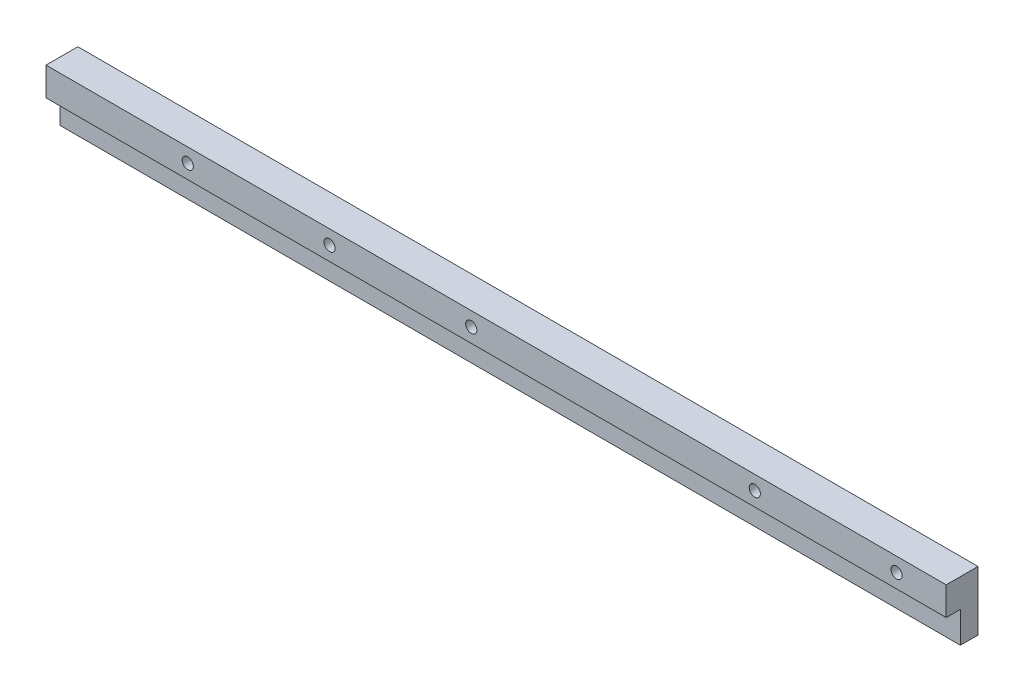
SolidWorks part; units mm, degrees
note: The reader was unsure of these and kept them because the rebuilt part matched: shared geometry of "Sketch2<3>".
ref_plane "Front Plane" through (0, 0, 0) normal (0, 0, 1) x (1, 0, 0)
ref_plane "Top Plane" through (0, 0, 0) normal (0, 1, 0) x (1, 0, 0)
ref_plane "Right Plane" through (0, 0, 0) normal (1, 0, 0) x (0, 0, -1)
sketch "Sketch1" plane through (0, 0, 0) normal (0, 0, 1) x (1, 0, 0)
  line L0 (6.5929, 7.3704) -> (176.701, 203.0574)
  line L1 (6.5929, 7.3704) -> (176.701, 7.3704)
  line L2 (176.701, 203.0574) -> (292.6093, 77.8877)
  line L3 (176.701, 203.0574) -> (176.701, 7.3704)
  line L4 (6.5929, 7.3704) -> (4.0986, 9.5386)
  line L6 (4.0986, 9.5386) -> (174.2067, 205.2256)
  line L10 (174.2067, 205.2256) -> (176.701, 203.0574)
  line L11 (292.6093, 77.8877) -> (294.8662, 79.9776)
  line L12 (294.8662, 79.9776) -> (176.701, 207.5845)
  line L13 (176.701, 203.0574) -> (176.701, 207.5845)
  line L14 (176.701, 207.5845) -> (174.2067, 205.2256)
  line L15 (4.0986, 9.5386) -> (6.5929, 7.3704)
  line L16 (6.5929, 7.3704) -> (9.3301, 4.6332)
  line L17 (9.3301, 4.6332) -> (179.222, 200.3349)
  line L18 (292.6093, 77.8877) -> (289.803, 75.306)
  line L19 (289.803, 75.306) -> (176.701, 197.4308)
  dimension "D1" = 42.8
  dimension "D3" = 90
  dimension "D4" = 90
  dimension "D5" = 41
extrude "Boss-Extrude1" add sketch "Sketch1" along normal blind 177.8 contours L10 L6 L4 L0 | L13 L14 L10 | L13 L2 L11 L12 | L1 L17 L3 L0 | L19 L18 L2 L17 | L3 L17 L2
ref_plane "Plane1" through (0, 0, 0) normal (0, 0, -1) x (-1, 0, 0)
sketch "Sketch2" plane through (0, 0, 0) normal (0, 0, -1) x (-1, 0, 0)
  line L4 (-294.8662, 79.9776) -> (-176.701, 207.5845) construction
  line L5 (-176.701, 207.5845) -> (-294.8662, 79.9776)
  line L6 (-176.701, 207.5845) -> (-4.0362, 9.4669)
  line L11 (-294.8662, 308.5776) -> (-4.0362, 308.5776)
  line L12 (-4.0362, 308.5776) -> (-4.0362, 9.4669)
  line L14 (-294.8662, 308.5776) -> (-294.8662, 79.9776)
  line L15 (-4.0986, 9.5386) -> (-174.2067, 205.2256) construction
  circle A6 centre (-109.5518, 215.6074) radius 6.35
  circle A7 centre (-50.0992, 143.6384) radius 6.35
  circle A8 centre (0, 64.0701) radius 6.35
  dimension "D4" = 94.0268
  dimension "D1" = 228.6
  dimension "D2" = 93.3497
  dimension "D3" = 290.83
extrude "Boss-Extrude2" add sketch "Sketch2" against normal blind 3.175
ref_plane "Plane2" through (0, 0, 177.8) normal (0, 0, 1) x (1, 0, 0)
ref_plane "Plane3" through (0, 0, 88.9) normal (0, 0, 1) x (1, 0, 0)
mirror "Mirror1" about plane through (0, 0, 88.9) normal (0, 0, 1) of "Boss-Extrude2"
sketch "Sketch3" plane through (-2.3884, 2.0762, 0) normal (-0.7547, 0.6561, 0) x (0.6561, 0.7547, 0)
  line L0 (0, -88.9) -> (269.1756, -88.9) construction
  line L1 (-55, -88.9) -> (55, -88.9) construction
  line L2 (269.1756, -174.625) -> (269.1756, -3.175) construction
  line L3 (9.8879, -115.3039) -> (147.0479, -115.3039)
  line L4 (147.0479, -115.3039) -> (146.9349, 0)
  line L5 (235.5345, 0) -> (9.7927, 0) construction
  line L6 (146.9349, 0) -> (210.4349, 0)
  line L7 (272.5923, 0) -> (9.7927, 0) construction
  line L8 (210.4349, 0) -> (210.4349, -115.3039)
  line L9 (210.4349, -115.3039) -> (147.0479, -115.3039)
  line L10 (147.0479, -115.3039) -> (210.4349, -115.3039)
  line L11 (9.8879, -174.625) -> (9.8879, -3.175) construction
  dimension "D1" = 63.5
  dimension "D3" = 137.16
extrude "Cut-Extrude1" cut sketch "Sketch3" against normal blind 7.62
sketch "Sketch4" plane through (0, 0, 3.175) normal (0, 0, 1) x (1, 0, 0)
  line L0 (176.701, 207.5845) -> (4.0362, 9.4669) construction
  circle A0 centre (115.1385, 136.947) radius 35.56
extrude "Cut-Extrude2" cut sketch "Sketch4" against normal blind 5.08
sketch "Sketch5" plane through (0, 0, 0) normal (0, 0, -1) x (-1, 0, 0)
  line L0 (-4.0362, 308.5776) -> (-4.0362, 9.4669) construction
  line L1 (-4.0362, 87.8093) -> (23.7187, 87.8093)
  line L2 (-4.0362, 87.8093) -> (-4.0362, 41.2582)
  line L3 (-4.0362, 41.2582) -> (23.7187, 41.2582)
  line L4 (23.7187, 87.8093) -> (23.7187, 41.2582)
  line L5 (-294.8662, 308.5776) -> (-4.0362, 308.5776) construction
  circle A0 centre (0, 64.0701) radius 6.35
  line M4 (-4.0362, 9.4669) -> (-4.0362, 308.5776)
extrude "Boss-Extrude3" add sketch "Sketch5" against normal blind 3.175 contours L4 L1 L3 A0 M4
sketch "Sketch6" plane through (0, 0, 177.8) normal (0, 0, 1) x (1, 0, 0)
  line L1 (4.0362, 87.8093) -> (-23.7187, 87.8093)
  line L2 (4.0362, 87.8093) -> (4.0362, 41.2582)
  line L3 (4.0362, 41.2582) -> (-23.7187, 41.2582)
  line L4 (-23.7187, 87.8093) -> (-23.7187, 41.2582)
  circle A0 centre (0, 64.0701) radius 6.35
  line M6 (4.0362, 308.5776) -> (4.0362, 9.4669)
extrude "Boss-Extrude4" add sketch "Sketch6" against normal blind 3.175 contours L1 L4 L3 A0 M6
extrude "Cut-Extrude3" cut sketch "Sketch2<3>" against normal blind 203.2 contours A8
sketch "Sketch2<3>" plane through (0, 0, 0) normal (0, 0, -1) x (-1, 0, 0) same geometry as "Sketch2"
sketch "Sketch7" plane through (198.615, 183.9195, 0) normal (0.7337, 0.6794, 0) x (0, 0, -1)
  line L0 (-174.625, -141.6623) -> (-3.175, -141.6623) construction
  line L1 (-3.175, -141.6623) -> (-88.9, -141.6623) construction
  line L2 (-88.9, -141.6623) -> (-88.9, -123.8823) construction
  line L3 (-88.9, 55) -> (-88.9, -55) construction
  line L4 (-88.9, -123.8823) -> (-36.6474, -123.8823) construction
  line L5 (-36.6474, -123.8823) -> (-36.6474, -141.6623) construction
  line L6 (-36.6474, -141.6623) -> (-140.9512, -141.6623) construction
  line L7 (-140.9512, -141.6623) -> (-140.9512, -123.8823) construction
  line L8 (-140.9512, -123.8823) -> (-88.9, -123.8823) construction
  line L10 (-140.9512, -123.8823) -> (-36.6474, -123.8823)
  line L11 (-140.9512, -123.8823) -> (-140.9512, -141.6623)
  line L12 (-140.9512, -141.6623) -> (-36.6474, -141.6623)
  line L13 (-36.6474, -123.8823) -> (-36.6474, -141.6623)
  dimension "D1" = 17.78
extrude "Cut-Extrude4" cut sketch "Sketch7" against normal blind 7.62
sketch "Sketch8" plane through (0, 0, 0) normal (0, 0, -1) x (-1, 0, 0)
  line L0 (-294.8662, 79.9776) -> (-294.8662, 191.7376) construction
  line L1 (-294.8662, 308.5776) -> (-294.8662, 79.9776) construction
sketch "Sketch9" plane through (294.8662, 0, 0) normal (1, 0, 0) x (0, 0, -1)
  line L1 (0, 186.7117) -> (5.0949, 186.7117)
  line L2 (0, 186.7117) -> (0, 196.8717)
  line L3 (0, 196.8717) -> (5.0949, 196.8717)
  line L4 (5.0949, 186.7117) -> (5.0949, 196.8717)
  line L5 (0, 308.5776) -> (0, 79.9776) construction
  line L6 (5.0949, 196.8717) -> (11.4058, 196.8717)
  line L7 (5.0949, 196.8717) -> (5.0949, 175.5607)
  line L8 (5.0949, 175.5607) -> (11.4058, 175.5607)
  line L9 (11.4058, 196.8717) -> (11.4058, 175.5607)
  line M1 (0, 79.9776) -> (0, 308.5776)
  dimension "D1" = 10.16
extrude "Boss-Extrude5" add sketch "Sketch9" against normal blind 373.38 contours L1 L4 L3 M1 | L9 L6 L4 L7 L8
ref_plane "Plane4" through (0, 0, 88.9) normal (0, 0, 1) x (1, 0, 0)
mirror "Mirror2" about plane through (0, 0, 88.9) normal (0, 0, 1) of "Boss-Extrude5"
sketch "Sketch10" plane through (294.8662, 0, 0) normal (1, 0, 0) x (0, 0, -1)
  line L0 (0, 308.5776) -> (0, 79.9776) construction
  line L1 (0, 205.7357) -> (16.3899, 205.7357)
  line L2 (0, 205.7357) -> (0, 149.8827)
  line L3 (0, 149.8827) -> (16.3899, 149.8827)
  line L4 (16.3899, 205.7357) -> (16.3899, 149.8827)
extrude "Cut-Extrude5" cut sketch "Sketch10" against normal blind 50.8
sketch "Sketch11" plane through (0, 0, 0) normal (0, 0, -1) x (-1, 0, 0)
  line L0 (-294.8662, 308.5776) -> (-294.8662, 79.9776) construction
  line L1 (-294.8662, 209.1619) -> (-257.555, 209.1619)
  line L2 (-294.8662, 209.1619) -> (-294.8662, 139.1254)
  line L3 (-294.8662, 139.1254) -> (-257.555, 139.1254)
  line L4 (-257.555, 209.1619) -> (-257.555, 139.1254)
extrude "Cut-Extrude6" cut sketch "Sketch11" against normal blind 63.5
sketch "Sketch12" plane through (198.615, 183.9195, 0) normal (0.7337, 0.6794, 0) x (0, 0, -1)
  line L0 (-171.533, 28.0226) -> (-143.202, -115.1621)
  line L1 (-33.4545, -115.1621) -> (-6.2281, 28.0226)
extrude "Cut-Extrude-Thin3" cut sketch "Sketch12" against normal blind 1.27 thin thin type one direction reverse wall 3.302
sketch "Sketch13" plane through (198.615, 183.9195, 0) normal (0.7337, 0.6794, 0) x (0, 0, -1)
  line L0 (-171.533, 28.0226) -> (-171.3752, 27.2252)
  line L1 (-171.3752, 27.2252) -> (-168.2938, 28.6635)
  line L2 (-168.2938, 28.6635) -> (-171.533, 28.0226)
  line L3 (-168.2938, 28.6635) -> (-139.9628, -114.5212) construction
  line L4 (-143.202, -115.1621) -> (-140.1206, -113.7238)
  line L5 (-140.1206, -113.7238) -> (-139.9628, -114.5212)
  line L6 (-143.202, -115.1621) -> (-139.9628, -114.5212)
  line L7 (-171.533, 28.0226) -> (-143.202, -115.1621) construction
  line L8 (-171.533, 28.0226) -> (-143.202, -115.1621) construction
  line L9 (-9.4719, 28.6394) -> (-6.3826, 27.2098)
  line L10 (-33.4545, -115.1621) -> (-6.2281, 28.0226) construction
  line L11 (-6.3826, 27.2098) -> (-6.2281, 28.0226)
  line L12 (-6.2281, 28.0226) -> (-9.4719, 28.6394)
  line L13 (-36.6984, -114.5453) -> (-33.3027, -114.3636)
  line L14 (-33.4545, -115.1621) -> (-6.2281, 28.0226) construction
  line L15 (-33.3027, -114.3636) -> (-33.4545, -115.1621)
  line L16 (-33.4545, -115.1621) -> (-36.6984, -114.5453)
  dimension "D1" = 0.8128
  dimension "D2" = 0.8128
  dimension "D3" = 0.8128
  dimension "D4" = 0.8128
extrude "Boss-Extrude6" add sketch "Sketch13" against normal blind 1.27 separate body
sketch "Sketch14" plane through (0, 0, 3.175) normal (0, 0, 1) x (1, 0, 0)
  line L0 (4.0362, 308.5776) -> (4.0362, 9.4669) construction
  circle A0 centre (25.6262, 167.7264) radius 6.35
  dimension "D1" = 21.59
extrude "Cut-Extrude7" cut sketch "Sketch14" against normal blind 6.35
sketch "Sketch15" plane through (0, 0, 177.8) normal (0, 0, 1) x (1, 0, 0)
  circle A0 centre (25.6262, 167.7264) radius 6.35
extrude "Cut-Extrude8" cut sketch "Sketch15" against normal blind 6.35
sketch "Sketch16" plane through (0, 0, -11.4058) normal (0, 0, -1) x (-1, 0, 0)
  line L0 (-244.0662, 191.7917) -> (-4.0362, 191.7917) construction
  line L1 (-244.0662, 196.8717) -> (-244.0662, 186.7117) construction
  line L2 (-4.0362, 308.5776) -> (-4.0362, 9.4669) construction
  line L3 (-4.0362, 191.7917) -> (78.5138, 191.7917) construction
  line L4 (78.5138, 196.8717) -> (78.5138, 175.5607) construction
  circle A0 centre (-226.2862, 191.7917) radius 2
  circle A1 centre (-175.4862, 191.7917) radius 2
  circle A2 centre (-73.8862, 191.7917) radius 2
  circle A3 centre (-23.0862, 191.7917) radius 2
  circle A4 centre (27.7138, 191.7917) radius 2
  dimension "D1" = 50.8
  dimension "D5" = 50.8
  dimension "D2" = 50.8
  dimension "D3" = 101.6
  dimension "D4" = 50.8
extrude "Cut-Extrude9" cut sketch "Sketch16" against normal blind 203.2
sketch "Sketch17" plane through (0, 0, 189.2058) normal (0, 0, 1) x (1, 0, 0)
  line L0 (226.2862, 191.7917) -> (294.8662, 191.7376) construction
  circle A0 centre (272.0062, 191.7376) radius 2
  dimension "D1" = 45.72
extrude "Cut-Extrude10" cut sketch "Sketch17" against normal blind 50.8
sketch "Sketch18" plane through (198.615, 183.9195, 0) normal (0.7337, 0.6794, 0) x (0, 0, -1)
  line L0 (-170.825, -33.5095) -> (-170.825, -115.9129)
  line L1 (-170.825, -115.9129) -> (-148.0215, -115.9129)
  line L2 (-148.0215, -115.9129) -> (-165.1241, -33.5095)
  line L3 (-165.1241, -33.5095) -> (-170.825, -33.5095)
extrude "Cut-Extrude11" cut sketch "Sketch18" against normal blind 50.8
sketch "Sketch19" plane through (198.615, 183.9195, 0) normal (0.7337, 0.6794, 0) x (0, 0, -1)
  line L0 (-27.791, -115.9129) -> (-12.8356, -35.3555)
  line L1 (-12.8356, -35.3555) -> (-7.2062, -35.3555)
  line L2 (-7.2062, -35.3555) -> (-7.2062, -115.9129)
  line L3 (-7.2062, -115.9129) -> (-27.791, -115.9129)
extrude "Cut-Extrude12" cut sketch "Sketch19" against normal blind 135.636
sketch "Sketch20" plane through (0, 0, 177.8) normal (0, 0, 1) x (1, 0, 0)
  line L0 (294.8662, 308.5776) -> (4.0362, 308.5776) construction
  line L1 (162.8579, 292.5756) -> (264.4579, 292.5756)
  line L2 (162.8579, 292.5756) -> (162.8579, 241.7756)
  line L3 (162.8579, 241.7756) -> (264.4579, 241.7756)
  line L4 (264.4579, 292.5756) -> (264.4579, 241.7756)
  line L5 (169.2079, 292.4947) -> (258.1079, 292.4947)
  line L6 (169.2079, 292.4947) -> (169.2079, 273.4447)
  line L7 (169.2079, 273.4447) -> (258.1079, 273.4447)
  line L8 (258.1079, 292.4947) -> (258.1079, 273.4447)
  circle A0 centre (162.8579, 241.7756) radius 1.55
  circle A1 centre (162.8579, 292.5756) radius 1.55
  circle A2 centre (264.4579, 292.5756) radius 1.55
  circle A3 centre (264.4579, 241.7756) radius 1.55
  dimension "D3" = 16.002
  dimension "D1" = 101.6
  dimension "D2" = 50.8
  dimension "D4" = 6.35
  dimension "D5" = 88.9
  dimension "D6" = 19.05
extrude "Cut-Extrude13" cut sketch "Sketch20" against normal blind 25.4 contours L2 A1 L1 | L1 A1 L2 | L4 A2 L1 | L1 A2 L4 | L2 A0 L3 | L3 A0 L2 | L4 A3 L3 | L3 A3 L4 | L8 L5 L6 L7
sketch "Sketch22" plane through (0, 0, 0) normal (0, 0, -1) x (-1, 0, 0)
  line L0 (-294.8662, 308.5776) -> (-4.0362, 308.5776) construction
  line L1 (-264.5816, 292.5756) -> (-162.9816, 292.5756)
  line L2 (-264.5816, 292.5756) -> (-264.5816, 241.7756)
  line L3 (-264.5816, 241.7756) -> (-162.9816, 241.7756)
  line L4 (-162.9816, 292.5756) -> (-162.9816, 241.7756)
  line L5 (-258.2316, 292.5534) -> (-169.3316, 292.5534)
  line L6 (-258.2316, 292.5534) -> (-258.2316, 273.5034)
  line L7 (-258.2316, 273.5034) -> (-169.3316, 273.5034)
  line L8 (-169.3316, 292.5534) -> (-169.3316, 273.5034)
  circle A0 centre (-264.5816, 292.5756) radius 1.55
  circle A1 centre (-264.5816, 241.7756) radius 1.55
  circle A2 centre (-162.9816, 292.5756) radius 1.55
  circle A3 centre (-162.9816, 241.7756) radius 1.55
  dimension "D3" = 16.002
  dimension "D1" = 101.6
  dimension "D2" = 50.8
  dimension "D4" = 6.35
  dimension "D5" = 88.9
  dimension "D6" = 19.05
extrude "Cut-Extrude14" cut sketch "Sketch22" against normal blind 25.4 contours L1 A0 L2 | L2 A0 L1 | L2 A1 L3 | L3 A1 L2 | L4 A2 L1 | L1 A2 L4 | L4 A3 L3 | L3 A3 L4 | L8 L5 L6 L7
sketch "Sketch23" plane through (0, 0, 0) normal (0, 0, -1) x (-1, 0, 0)
  line L0 (-292.2866, 77.5908) -> (-174.4076, 204.953) construction
  line L1 (-292.6093, 77.8877) -> (-289.803, 75.306) construction
  line L2 (-176.701, 207.5845) -> (-4.0362, 9.4669) construction
  line L3 (-7.2586, 7.3704) -> (-177.0204, 202.13)
  line L4 (-6.5929, 7.3704) -> (-11.7063, 7.3704) construction
  circle A0 centre (-282.4885, 88.1771) radius 1.5
  circle A1 centre (-262.696, 109.5619) radius 1.5
  circle A2 centre (-243.4899, 130.3131) radius 1.5
  circle A3 centre (-222.238, 153.2747) radius 1.5
  circle A4 centre (-17.5669, 19.1965) radius 1.5
  circle A5 centre (-33.1684, 37.0955) radius 1.5
  circle A6 centre (-50.887, 57.4232) radius 1.5
  circle A7 centre (-147.3861, 168.1319) radius 1.5
  circle A8 centre (-72.1847, 81.857) radius 1.5
extrude "Cut-Extrude15" cut sketch "Sketch23" against normal blind 12.7 contours A0 L0 | L0 A0 | A1 L0 | L0 A1 | A2 L0 | L0 A2 | A3 L0 | L0 A3 | L3 A7 | L3 A7 | L3 A6 | L3 A6 | L3 A5 | L3 A5 | L3 A4 | L3 A4
sketch "Sketch24" plane through (0, 0, 177.8) normal (0, 0, 1) x (1, 0, 0)
  line L0 (7.3883, 7.3704) -> (179.0187, 205.0816) construction
  line L1 (6.5929, 7.3704) -> (11.7063, 7.3704) construction
  line L2 (176.701, 207.5845) -> (294.8662, 79.9776) construction
  line L3 (292.1599, 77.4743) -> (174.5457, 205.1115) construction
  line L4 (176.701, 207.5845) -> (4.0362, 9.4669) construction
  line L5 (292.6093, 77.8877) -> (289.803, 75.306) construction
  circle A0 centre (277.2218, 93.6853) radius 1.5
  circle A1 centre (256.088, 116.6201) radius 1.5
  circle A2 centre (233.3528, 141.2929) radius 1.5
  circle A3 centre (211.7585, 164.7274) radius 1.5
  circle A4 centre (135.0206, 154.3977) radius 1.5
  circle A5 centre (113.6721, 129.805) radius 1.5
  circle A6 centre (89.5465, 102.0133) radius 1.5
  circle A7 centre (62.6765, 71.0602) radius 1.5
  circle A8 centre (39.5224, 44.3875) radius 1.5
extrude "Cut-Extrude16" cut sketch "Sketch24" against normal blind 12.7
sketch "Sketch25" plane through (294.8662, 0, 0) normal (1, 0, 0) x (0, 0, -1)
  line L1 (0, 308.5776) -> (-227.8286, 308.5776)
  line L2 (0, 308.5776) -> (0, -56.3359)
  line L3 (0, -56.3359) -> (-227.8286, -56.3359)
  line L4 (-227.8286, 308.5776) -> (-227.8286, -56.3359)
extrude "Cut-Extrude17" cut sketch "Sketch25" against normal blind 381
ref_plane "Plane5" through (82.7762, 0, 0) normal (-1, 0, 0) x (0, 0, 1)
sketch "Sketch26" plane through (82.7762, 0, 0) normal (-1, 0, 0) x (0, 0, 1)
  line L1 (-11.4058, 196.8717) -> (0.3273, 196.8717)
  line L2 (-11.4058, 196.8717) -> (-11.4058, 175.3578)
  line L3 (-11.4058, 175.3578) -> (0.3273, 175.3578)
  line L4 (0.3273, 196.8717) -> (0.3273, 175.3578)
